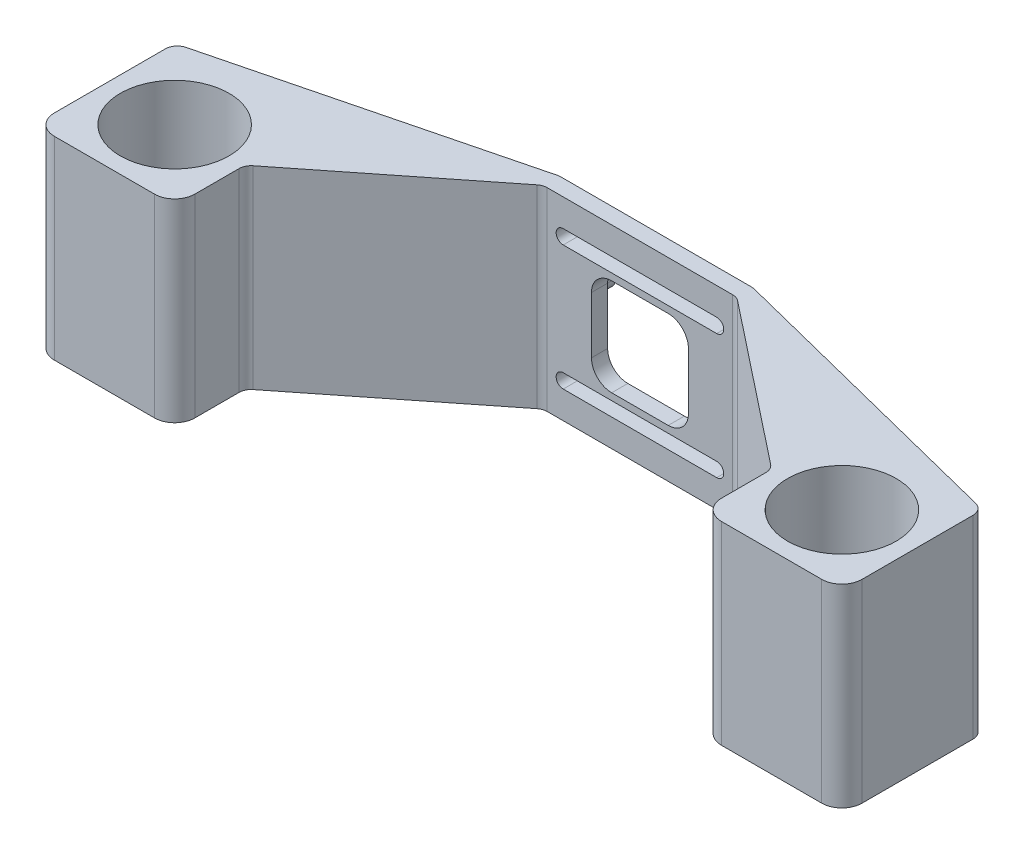
SolidWorks part; units mm, degrees
ref_plane "Front Plane" through (0, 0, 0) normal (0, 0, 1) x (1, 0, 0)
ref_plane "Top Plane" through (0, 0, 0) normal (0, 1, 0) x (1, 0, 0)
ref_plane "Right Plane" through (0, 0, 0) normal (1, 0, 0) x (0, 0, -1)
sketch "Sketch2" plane through (0, 0, 0) normal (0, 1, 0) x (1, 0, 0)
  line L0 (-17.4, -17.4) -> (82.6, -17.4) construction
  line L1 (-17.4, -17.4) -> (17.4, -17.4)
  line L2 (-17.4, -17.4) -> (-17.4, 17.4)
  line L5 (0, 17.4) -> (0, -17.4) construction
  line L6 (-17.4, 0) -> (17.4, 0) construction
  line L7 (82.6, -17.4) -> (82.6, 36.6) construction
  line L8 (17.4, -17.4) -> (17.4, 0)
  line L9 (82.6, 36.6) -> (58.6, 36.6)
  line L10 (82.6, 36.6) -> (82.6, 32.6)
  line L11 (82.6, 32.6) -> (58.6, 32.6)
  line L13 (17.4, 0) -> (58.6, 32.6)
  line L14 (58.6, 36.6) -> (-17.4, 17.4)
  circle A0 centre (0, 0) radius 13.45
  point P0 (0, 0)
  dimension "D3" = 26.9
  dimension "D8" = 17.4
  dimension "D9" = 17.4
  dimension "D1" = 34.8
  dimension "D2" = 34.8
  dimension "D4" = 100
  dimension "D5" = 54
  dimension "D6" = 24
  dimension "D7" = 4
extrude "Boss-Extrude1" add sketch "Sketch2" along normal blind 48
sketch3d "3DSketch1"
  line L0 (82.6, 0, -36.6) -> (82.6, 0, -32.6) construction
  line L1 (82.6, 0, -32.6) -> (82.6, 48, -32.6) construction
ref_plane "Plane1" through (82.6, 0, 0) normal (1, 0, 0) x (0, 0, -1)
mirror "Mirror1" about plane through (82.6, 0, 0) normal (1, 0, 0) of "Boss-Extrude1"
sketch "Sketch4" plane through (0, 0, -36.6) normal (0, 0, -1) x (-1, 0, 0)
  line L0 (-106.6, 24) -> (-58.6, 24) construction
  line L1 (-58.6, 48) -> (-58.6, 0) construction
  line L2 (-101.6, 8.55) -> (-63.6, 8.55) construction
  line L3 (-101.6, 10.3) -> (-63.6, 10.3)
  line L4 (-82.6, 0) -> (-82.6, 48) construction
  line L5 (-101.6, 6.8) -> (-63.6, 6.8)
  line L6 (-101.6, 39.45) -> (-63.6, 39.45) construction
  line L7 (-101.6, 37.7) -> (-63.6, 37.7)
  line L8 (-101.6, 41.2) -> (-63.6, 41.2)
  line L10 (-89.6, 12) -> (-75.6, 12)
  line L11 (-94.6, 17) -> (-94.6, 31)
  line L12 (-89.6, 36) -> (-75.6, 36)
  line L13 (-70.6, 17) -> (-70.6, 31)
  line L14 (-94.6, 12) -> (-70.6, 36) construction
  line L15 (-94.6, 36) -> (-70.6, 12) construction
  arc A0 (-101.6, 10.3) -> (-101.6, 6.8) centre (-101.6, 8.55) ccw
  arc A1 (-63.6, 6.8) -> (-63.6, 10.3) centre (-63.6, 8.55) ccw
  arc A2 (-101.6, 37.7) -> (-101.6, 41.2) centre (-101.6, 39.45) cw
  arc A3 (-63.6, 41.2) -> (-63.6, 37.7) centre (-63.6, 39.45) cw
  arc A5 (-94.6, 17) -> (-89.6, 12) centre (-89.6, 17) ccw
  arc A6 (-75.6, 12) -> (-70.6, 17) centre (-75.6, 17) ccw
  arc A7 (-70.6, 31) -> (-75.6, 36) centre (-75.6, 31) ccw
  arc A8 (-94.6, 31) -> (-89.6, 36) centre (-89.6, 31) cw
  circle A9 centre (-82.6, 24) radius 12 construction
  point P5 (-82.6, 24)
  point P7 (-82.6, 8.55)
  point P10 (-82.6, 24)
  point P17 (-82.6, 39.45)
  dimension "D4" = 24
  dimension "D6" = 5
  dimension "D1" = 15.45
  dimension "D2" = 1.75
  dimension "D3" = 38
  dimension "D5" = 24
extrude "Cut-Extrude1" cut sketch "Sketch4" against normal blind 10
ref_plane "Plane2" through (0, 0, -36.6) normal (0, 0, -1) x (-1, 0, 0)
sketch "Sketch5" plane through (0, 0, -36.6) normal (0, 0, -1) x (-1, 0, 0)
  line L0 (-107.3963, 24) -> (-21.5979, 24) construction
  line L1 (-82.6, 2.2) -> (-82.6, -2.2) construction
  line L2 (-106.6, 24) -> (-58.6, 24) construction
  line L3 (-59.6, 31) -> (-45.6, 31)
  line L4 (-59.6, 31) -> (-59.6, 17)
  line L5 (-59.6, 17) -> (-45.6, 17)
  line L6 (-45.6, 31) -> (-45.6, 17)
  line L7 (-59.6, 31) -> (-45.6, 17) construction
  line L8 (-59.6, 17) -> (-45.6, 31) construction
  circle A0 centre (-52.6, 24) radius 4.1
  dimension "D1" = 8.2
  dimension "D2" = 30
  dimension "D3" = 14
  dimension "D4" = 14
extrude "Boss-Extrude2" add sketch "Sketch5" along normal blind 13 and the other way blind 4
fillet "Fillet1" radius 3 4 edges at (59.6, 31, -43.1) (59.6, 17, -43.1) (45.6, 31, -41.4579) (45.6, 17, -41.4579)
fillet "Fillet3" radius 3 9 edges at (-17.4, 24, -17.4) (58.6, 39.118, -36.6) (58.6, 8.882, -36.6) (106.6, 24, -36.6) (17.4, 24, 0) (58.6, 24, -32.6) (106.6, 24, -32.6) (147.8, 24, 0) (182.6, 24, -17.4)
fillet "Fillet4" radius 5 4 edges at (-17.4, 24, 17.4) (17.4, 24, 17.4) (147.8, 24, 17.4) (182.6, 24, 17.4)
sketch "Sketch6" plane through (0, 0, -36.6) normal (0, 0, -1) x (-1, 0, 0)
  circle A0 centre (-52.6, 24) radius 4.1 construction
  circle A1 centre (-52.6, 24) radius 4.1
